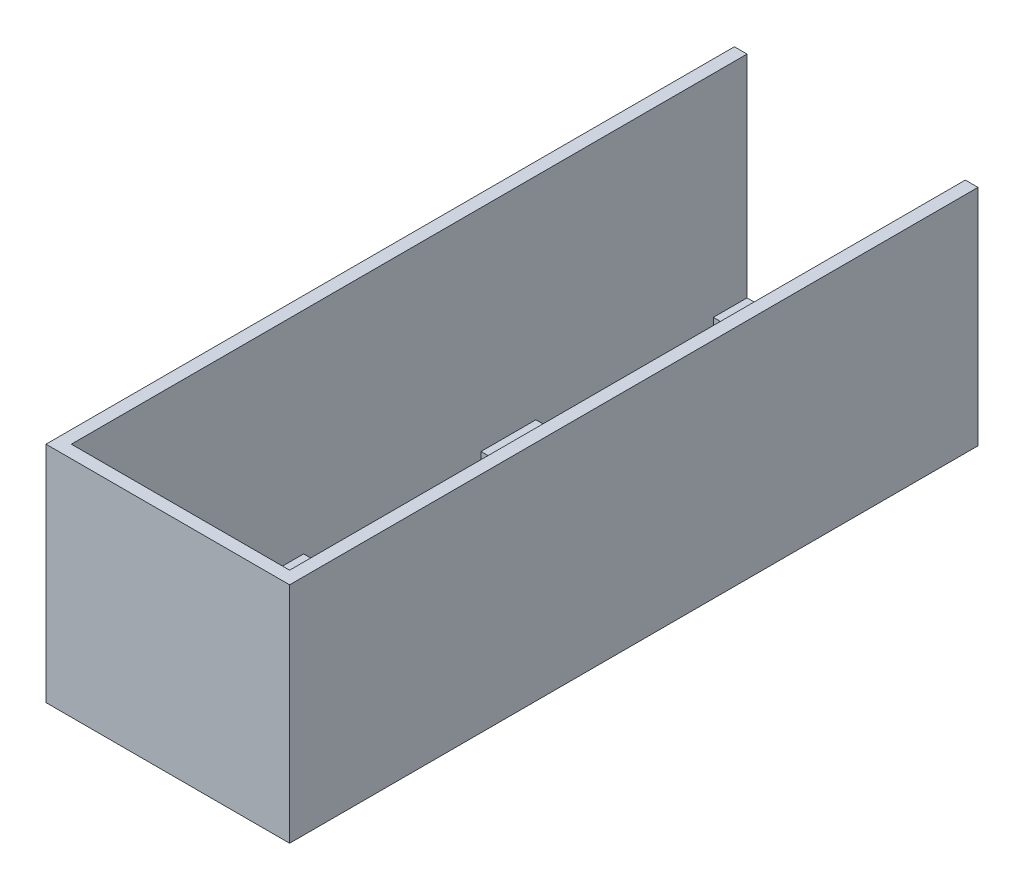
SolidWorks part; units mm, degrees
ref_plane "Front Plane" through (0, 0, 0) normal (0, 0, 1) x (1, 0, 0)
ref_plane "Top Plane" through (0, 0, 0) normal (0, 1, 0) x (1, 0, 0)
ref_plane "Right Plane" through (0, 0, 0) normal (1, 0, 0) x (0, 0, -1)
sketch "Sketch1" plane through (0, 0, 0) normal (0, 0, 1) x (1, 0, 0)
  line L0 (0, 0) -> (0, -20)
  line L1 (0, -20) -> (0, -50)
  line L2 (0, -50) -> (51.6786, -50)
  line L5 (-3, 0) -> (-3, -20)
  line L6 (-3, -20) -> (-3, -53)
  line L7 (-3, -53) -> (54.6786, -53)
  line L10 (-3, 0) -> (0, 0)
  line L12 (51.6786, -50) -> (51.6786, 0)
  line L13 (51.6786, -50) -> (51.6786, 37.6119) construction
  line L14 (51.6786, 37.6119) -> (67.0297, -2.1736) construction
  line L15 (54.6786, -53) -> (54.6786, 21.503) construction
  line L16 (54.6786, 21.503) -> (64.2308, -3.2535) construction
  line L17 (51.6786, 0) -> (54.6786, 0)
  line L18 (54.6786, 0) -> (54.6786, -53)
  point P13 (55, -53.8342)
  point P15 (2.44, -49.7784)
  point P17 (55.4206, -38.2559)
  point P18 (54.6439, -55.0048)
  dimension "D2" = 20
  dimension "D3" = 30
  dimension "D5" = 3
  dimension "D1" = 3
extrude "Boss-Extrude1" add sketch "Sketch1" along normal blind 160
sketch "Sketch2" plane through (0, 0, 0) normal (0, 1, 0) x (1, 0, 0)
  line L0 (51.6786, -160) -> (0, -160) construction
  line L1 (45, -8) -> (0, -8)
  line L2 (45, -8) -> (45, -50)
  line L3 (45, -50) -> (0, -50)
  line L4 (0, -8) -> (0, -50)
  line L5 (45, -63) -> (0, -63)
  line L6 (45, -63) -> (45, -105)
  line L7 (45, -105) -> (0, -105)
  line L8 (0, -63) -> (0, -105)
  line L9 (45, -118) -> (0, -118)
  line L10 (45, -118) -> (45, -160)
  line L11 (45, -160) -> (0, -160)
  line L12 (0, -118) -> (0, -160)
  line L13 (0, -160) -> (0, 0) construction
  dimension "D1" = 42
  dimension "D2" = 13
  dimension "D3" = 42
  dimension "D4" = 13
  dimension "D5" = 42
  dimension "D6" = 45
extrude "Cut-Extrude1" cut sketch "Sketch2" against normal through all
sketch "Sketch3" plane through (0, 0, 160) normal (0, 0, 1) x (1, 0, 0)
  line L0 (-3, 0) -> (54.6786, 0)
  line L1 (54.6786, 0) -> (54.6786, -53)
  line L2 (54.6786, -53) -> (0, -53)
  line L10 (0, 0) -> (-3, 0)
  line L11 (-3, 0) -> (-3, -53)
  line L13 (-3, -53) -> (0, -53)
  line L18 (0, -53) -> (0, 0)
  line L21 (-3, 0) -> (-3, -53)
  line L23 (-3, -53) -> (0, -53)
  dimension "D1" = 0
extrude "Boss-Extrude2" add sketch "Sketch3" along normal blind 3
